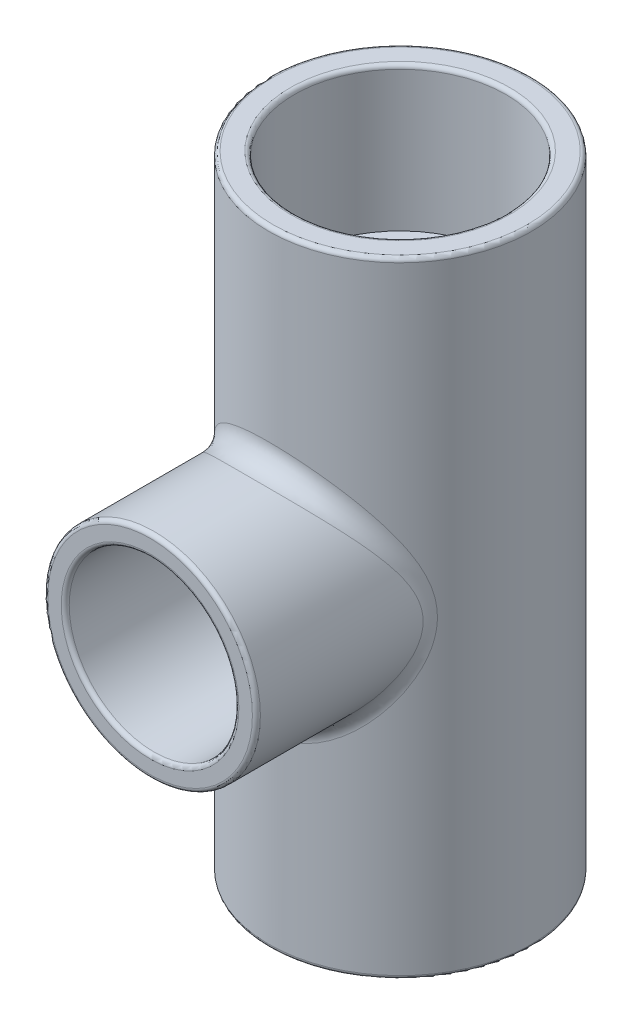
SolidWorks part; units mm, degrees
ref_plane "Front Plane" through (0, 0, 0) normal (0, 0, 1) x (1, 0, 0)
ref_plane "Top Plane" through (0, 0, 0) normal (0, 1, 0) x (1, 0, 0)
ref_plane "Right Plane" through (0, 0, 0) normal (1, 0, 0) x (0, 0, -1)
sketch "Sketch1" plane through (0, 0, 0) normal (0, 1, 0) x (1, 0, 0)
  circle A0 centre (0, 0) radius 412
  circle A1 centre (0, 0) radius 656.5
  dimension "D1" = 824
  dimension "D2" = 1313
extrude "Boss-Extrude1" add sketch "Sketch1" along normal blind 3125
sketch "Sketch2" plane through (0, 3125, 0) normal (0, 1, 0) x (1, 0, 0)
  circle A0 centre (0, 0) radius 529
  dimension "D1" = 1058
extrude "Cut-Extrude1" cut sketch "Sketch2" against normal blind 720
sketch "Sketch3" plane through (0, 0, 0) normal (0, -1, 0) x (1, 0, 0)
  circle A0 centre (0, 0) radius 529
  dimension "D1" = 1058
extrude "Cut-Extrude2" cut sketch "Sketch3" against normal blind 720
sketch "Sketch4" plane through (0, 0, 0) normal (0, 0, 1) x (1, 0, 0)
  line L0 (529, 3125) -> (-529, 3125) construction
  line L1 (0, 3125) -> (0, 0) construction
  circle A0 centre (0, 1562.5) radius 531.5
  circle A1 centre (0, 1562.5) radius 311
  dimension "D1" = 1063
  dimension "D2" = 622
  dimension "D3" = 1562.5
extrude "Boss-Extrude2" add sketch "Sketch4" along normal blind 1250
sketch "Sketch5" plane through (0, 0, 1250) normal (0, 0, 1) x (1, 0, 0)
  circle A0 centre (0, 1562.5) radius 424
  dimension "D1" = 848
extrude "Cut-Extrude4" cut sketch "Sketch5" against normal blind 690
sketch "Sketch6" plane through (0, 0, 0) normal (0, 1, 0) x (1, 0, 0)
  line L0 (412, 0) -> (-412, 0) construction
  circle A0 centre (0, 0) radius 412
extrude "Cut-Extrude5" cut sketch "Sketch6" along normal through all
sketch "Sketch7" plane through (0, 0, 560) normal (0, 0, 1) x (1, 0, 0)
  circle A0 centre (0, 1555.9513) radius 311
  dimension "D1" = 622
extrude "Cut-Extrude6" cut sketch "Sketch7" against normal blind 690
fillet "Fillet1" radius 100 1 edges at (524.4649, 1648.6906, 394.8782)
fillet "Fillet2" radius 20 2 edges at (0, 3125, 656.5) (0, 3125, 529)
fillet "Fillet3" radius 20 2 edges at (0, 0, 656.5) (0, 0, -529)
fillet "Fillet4" radius 20 2 edges at (531.5, 1562.5, 1250) (424, 1562.5, 1250)
